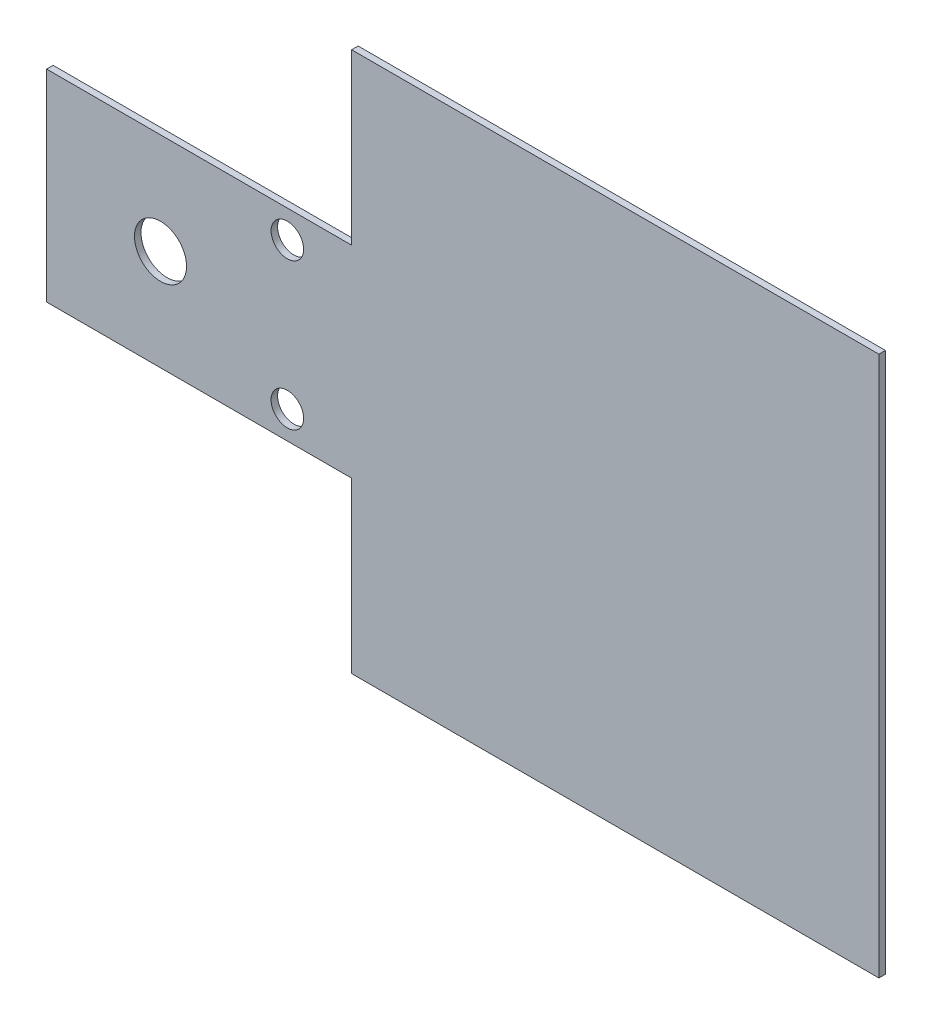
SolidWorks part; units mm, degrees
material "201 Annealed Stainless Steel (SS)"
ref_plane "Front Plane" through (0, 0, 0) normal (0, 0, 1) x (1, 0, 0)
ref_plane "Top Plane" through (0, 0, 0) normal (0, 1, 0) x (1, 0, 0)
ref_plane "Right Plane" through (0, 0, 0) normal (1, 0, 0) x (0, 0, -1)
sketch "Sketch1" plane through (0, 0, 0) normal (0, 0, 1) x (1, 0, 0)
  line L1 (-81, -120) -> (81, -120)
  line L2 (-81, -120) -> (-81, 120)
  line L3 (-81, 120) -> (81, 120)
  line L4 (81, -120) -> (81, 120)
  line L5 (-81, -120) -> (81, 120) construction
  line L6 (-81, 120) -> (81, -120) construction
  point P0 (0, 0)
  dimension "D1" = 162
  dimension "D2" = 240
extrude "Boss-Extrude1" add sketch "Sketch1" along normal blind 2
sketch "Sketch2" [suppressed] plane through (0, 0, 0) normal (0, 0, -1) x (-1, 0, 0)
  line L0 (61, 200) -> (61, -200) construction
  line L1 (-61, 314.7216) -> (-204.3993, 314.7216)
  line L2 (-61, 314.7216) -> (-61, -251.9618)
  line L3 (-61, -251.9618) -> (-204.3993, -251.9618)
  line L4 (-204.3993, 314.7216) -> (-204.3993, -251.9618)
  line L6 (61, 279.3211) -> (244.4765, 279.3211)
  line L7 (61, 279.3211) -> (61, -295.1839)
  line L8 (61, -295.1839) -> (244.4765, -295.1839)
  line L9 (244.4765, 279.3211) -> (244.4765, -295.1839)
  line L10 (-61, -200) -> (-61, -140) construction
  dimension "D1" = 122
extrude "Cut-Extrude1" [suppressed] cut sketch "Sketch2" against normal through all
sketch "Sketch3" [suppressed] plane through (75, 0, 0) normal (1, 0, 0) x (0, 0, -1)
  line L0 (-2, 90) -> (0, 90) construction
  line L1 (-2, 90) -> (-2, -90) construction
  circle A0 centre (-7, 75) radius 2.5
  dimension "D3" = 5
  dimension "D1" = 15
  dimension "D2" = 5
surface "Surface-Extrude1" [suppressed] sketch "Sketch3"
sketch "Sketch4" plane through (-81, 0, 0) normal (-1, 0, 0) x (0, 0, 1)
  line L1 (2, 120) -> (0, 120) construction
  line L2 (0, -120) -> (0, 120) construction
  point P0 (7.5, 116)
  dimension "D1" = 4
  dimension "D2" = 7.5
ref_axis "Axis1" through (-81, 116, 7.5) along (1, 0, 0)
sketch "Sketch5" [suppressed] plane through (0, 0, 0) normal (0, 0, -1) x (-1, 0, 0)
  line L0 (49, 80) -> (49, -80) construction
  line L1 (-49, 80) -> (49, 80)
  line L2 (-49, 80) -> (-49, 60.2594)
  line L3 (-49, 60.2594) -> (49, 60.2594)
  line L4 (49, 80) -> (49, 60.2594)
extrude "Cut-Extrude2" [suppressed] cut sketch "Sketch5" against normal blind 3
sketch "Sketch6" [suppressed] plane through (0, 0, 2) normal (0, 0, 1) x (1, 0, 0)
  line L0 (0, 0) -> (103.2002, 0) construction
  line L1 (-40, 80) -> (-40, 108.3319) construction
  line L2 (-40, 80) -> (-27.987, 80) construction
  line L3 (0, 0) -> (0, 138.3235) construction
  line L4 (40, 80) -> (27.987, 80) construction
  line L5 (40, 80) -> (40, 108.3319) construction
  line L6 (40, -80) -> (40, -108.3319) construction
  line L7 (40, -80) -> (27.987, -80) construction
  line L8 (-40, -80) -> (-27.987, -80) construction
  line L9 (-40, -80) -> (-40, -108.3319) construction
  circle A0 centre (-40, 80) radius 4.5
  circle A2 centre (-45.8, 85.8) radius 1.95
  circle A3 centre (-45.8, 74.2) radius 1.95
  circle A4 centre (-34.2, 74.2) radius 1.95
  circle A5 centre (-34.2, 85.8) radius 1.95
  circle A6 centre (34.2, 85.8) radius 1.95
  circle A7 centre (34.2, 74.2) radius 1.95
  circle A8 centre (45.8, 74.2) radius 1.95
  circle A9 centre (45.8, 85.8) radius 1.95
  circle A10 centre (40, 80) radius 4.5
  circle A11 centre (40, -80) radius 4.5
  circle A12 centre (45.8, -85.8) radius 1.95
  circle A13 centre (45.8, -74.2) radius 1.95
  circle A14 centre (34.2, -74.2) radius 1.95
  circle A15 centre (34.2, -85.8) radius 1.95
  circle A16 centre (-34.2, -85.8) radius 1.95
  circle A17 centre (-34.2, -74.2) radius 1.95
  circle A18 centre (-45.8, -74.2) radius 1.95
  circle A19 centre (-45.8, -85.8) radius 1.95
  circle A20 centre (-40, -80) radius 4.5
  circle A21 centre (-40, 80) radius 5.1 construction
  dimension "D1" = 9
  dimension "D3" = 3.9
extrude "Leandut_holes" [suppressed] cut sketch "Sketch6" against normal through all
chamfer "Chamfer1" [suppressed] distance 5 angle 45
sketch "Sketch7" plane through (0, 0, 2) normal (0, 0, 1) x (1, 0, 0)
  line L0 (81, 120) -> (-81, 120) construction
  line L1 (-31, -125) -> (31, -125)
  line L2 (-31, -125) -> (-31, 100)
  line L3 (-31, 100) -> (31, 100)
  line L4 (31, -125) -> (31, 100)
  line L5 (0, 0) -> (0, -66.8576) construction
  line L7 (-81, 120) -> (-81, -120) construction
  point P0 (0, 0)
  dimension "D1" = 20
  dimension "D2" = 50
  dimension "D3" = 62
  dimension "D4" = 125
extrude "Plunger-Window" [suppressed] cut sketch "Sketch7" against normal through all
sketch "Sketch8" [suppressed] plane through (0, 0, 2) normal (0, 0, 1) x (1, 0, 0)
  line L0 (106, 145) -> (56, 145) construction
  line L1 (-56, 125) -> (56, 125)
  line L2 (-56, 125) -> (-56, 145)
  line L3 (-56, 145) -> (56, 145)
  line L4 (56, 125) -> (56, 145)
  line L5 (56, -110) -> (56, 125) construction
extrude "Cut-Extrude3" [suppressed] cut sketch "Sketch8" against normal blind 5
sketch "Sketch9" plane through (0, 0, 0) normal (0, 0, -1) x (-1, 0, 0)
  line L0 (1.1, 0) -> (-1.1, 0) construction
  line L5 (6, -100) -> (-6, -100)
  line L6 (6, -100) -> (6, 100)
  line L7 (6, 100) -> (-6, 100)
  line L8 (-6, -100) -> (-6, 100)
  line L9 (-81, 120) -> (81, 120) construction
  point P0 (0, 0)
  point P8 (0, 100)
  dimension "D1" = 12
  dimension "D2" = 100
  dimension "D3" = 100
  dimension "D4" = 20
extrude "Plunger-cutout" [suppressed] cut sketch "Sketch9" against normal through all and the other way through all
sketch "Sketch10" plane through (0, 0, 0) normal (0, 0, -1) x (-1, 0, 0)
  line L0 (81, -147.5) -> (209.9137, 21.8916) construction
  line L1 (81, 120) -> (81, -120) construction
  line L2 (81, 120) -> (209.9137, 21.8916) construction
  line L3 (81, 120) -> (81, -147.5) construction
  line L4 (-81, 120) -> (81, 120) construction
  line L5 (-81, 120) -> (81, 120) construction
  line L6 (0, 120) -> (0, 262.0874) construction
  line L7 (-81, 120) -> (-81, -147.5)
  line L8 (-81, 120) -> (-209.9137, 21.8916)
  line L9 (-81, -147.5) -> (-209.9137, 21.8916)
  line L10 (81, 120) -> (81, -120) construction
  dimension "D1" = 147.5
  dimension "D2" = 162
  dimension "D3" = 162
  dimension "D4" = 212.8667
  dimension "D5" = 240
extrude "Boss-Extrude3" [suppressed] add sketch "Sketch10" against normal through all
sketch "Sketch11" [suppressed] plane through (0, 0, 2) normal (0, 0, 1) x (1, 0, 0)
  line L0 (81, 217.5) -> (81, -274.1687)
split line "Split Line1" [suppressed]
sketch "Sketch12" plane through (0, 0, 0) normal (0, 0, -1) x (-1, 0, 0)
  line L0 (81, 120) -> (81, -120) construction
  line L4 (106.722, 31) -> (106.722, -31)
  line L5 (174.722, 31) -> (106.722, 31)
  line L6 (174.722, -31) -> (174.722, 31)
  line L7 (106.722, -31) -> (174.722, -31)
  line L8 (81, 31) -> (81, -31)
  line L9 (174.722, 31) -> (81, 31)
  line L10 (174.722, -31) -> (174.722, 31)
  line L11 (81, -31) -> (174.722, -31)
  circle A0 centre (139.72, 0) radius 8
  circle A4 centre (100.7508, -22.5) radius 5 construction
  circle A5 centre (100.7508, 22.5) radius 5 construction
  circle A6 centre (100.7508, -22.5) radius 5
  circle A7 centre (100.7508, 22.5) radius 5
  dimension "D3" = 16
  dimension "D5" = 139.72
  dimension "D1" = 0
extrude "Boss-Extrude4" add sketch "Sketch12" against normal through all
sketch "Sketch13" plane through (0, 0, 0) normal (0, 0, -1) x (-1, 0, 0)
  line L0 (0, 0) -> (-166.9371, 0) construction
  line L1 (108.207, -83) -> (-114.7867, -83)
  line L2 (108.207, -83) -> (108.207, -160.524)
  line L3 (108.207, -160.524) -> (-114.7867, -160.524)
  line L4 (-114.7867, -83) -> (-114.7867, -160.524)
  line L5 (-103.1423, 83) -> (143.0141, 83)
  line L6 (-103.1423, 83) -> (-103.1423, 164.1211)
  line L7 (-103.1423, 164.1211) -> (143.0141, 164.1211)
  line L8 (143.0141, 83) -> (143.0141, 164.1211)
  dimension "D1" = 166
extrude "Cut-Extrude4" cut sketch "Sketch13" against normal through all
